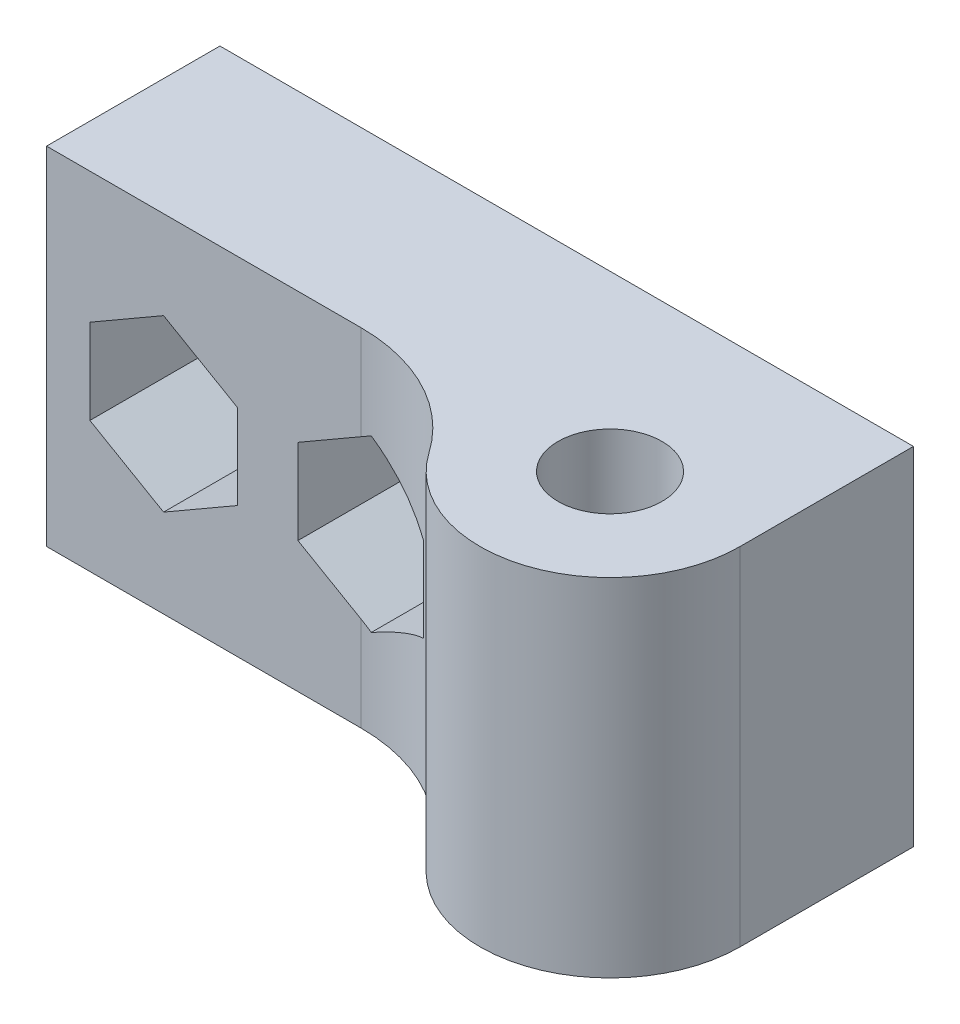
SolidWorks part; units mm, degrees
ref_plane "Front Plane" through (0, 0, 0) normal (0, 0, 1) x (1, 0, 0)
ref_plane "Top Plane" through (0, 0, 0) normal (0, 1, 0) x (1, 0, 0)
ref_plane "Right Plane" through (0, 0, 0) normal (1, 0, 0) x (0, 0, -1)
sketch "Sketch1" plane through (0, 0, 0) normal (0, 0, 1) x (1, 0, 0)
  line L1 (-20, 0) -> (20, 0)
  line L2 (-20, 0) -> (-20, -20)
  line L3 (-20, -20) -> (20, -20)
  line L4 (20, 0) -> (20, -20)
  point P4 (0, 0)
  dimension "D1" = 40
  dimension "D2" = 20
extrude "Boss-Extrude1" add sketch "Sketch1" along normal blind 10
sketch "Sketch2" plane through (0, 0, 10) normal (0, 0, 1) x (1, 0, 0)
  line L0 (-20, -10) -> (-13.25, -10) construction
  line L1 (-13.25, -14.9075) -> (-9, -12.4537)
  line L2 (-9, -12.4537) -> (-9, -7.5463)
  line L3 (-9, -7.5463) -> (-13.25, -5.0925)
  line L4 (-13.25, -5.0925) -> (-17.5, -7.5463)
  line L5 (-17.5, -7.5463) -> (-17.5, -12.4537)
  line L6 (-17.5, -12.4537) -> (-13.25, -14.9075)
  line L7 (-20, 0) -> (-20, -20) construction
  line L8 (-13.25, -5.0925) -> (-13.25, -10) construction
  circle A0 centre (-13.25, -10) radius 4.25 construction
  dimension "D1" = 8.5
  dimension "D2" = 2.5
extrude "Cut-Extrude1" cut sketch "Sketch2" against normal blind 7.5
sketch "Sketch5" plane through (0, 0, 2.5) normal (0, 0, 1) x (1, 0, 0)
  line L0 (-13.25, -5.0925) -> (-13.25, -14.9075) construction
  circle A0 centre (-13.25, -10) radius 2.75
  dimension "D1" = 5.5
extrude "Cut-Extrude3" cut sketch "Sketch5" against normal through all
pattern_linear "LPattern1" count 2 spacing 12 along (1, 0, 0) of "Cut-Extrude3", "Cut-Extrude1"
sketch "Sketch3" plane through (0, 0, 0) normal (0, 1, 0) x (1, 0, 0)
  line L1 (20, -10) -> (-20, -10) construction
  line L2 (20, -10) -> (20, 0) construction
  circle A0 centre (12.5, -10) radius 7.5
  dimension "D1" = 15
extrude "Boss-Extrude2" add sketch "Sketch3" against normal through all
sketch "Sketch4" plane through (0, 0, 0) normal (0, 1, 0) x (1, 0, 0)
  circle A0 centre (12.5, -10) radius 3
  arc A1 (5, -10) -> (20, -10) centre (12.5, -10) ccw construction
  dimension "D1" = 6
extrude "Cut-Extrude2" cut sketch "Sketch4" against normal through all
fillet "Fillet1" radius 10 1 edges at (5, -10, 10)
